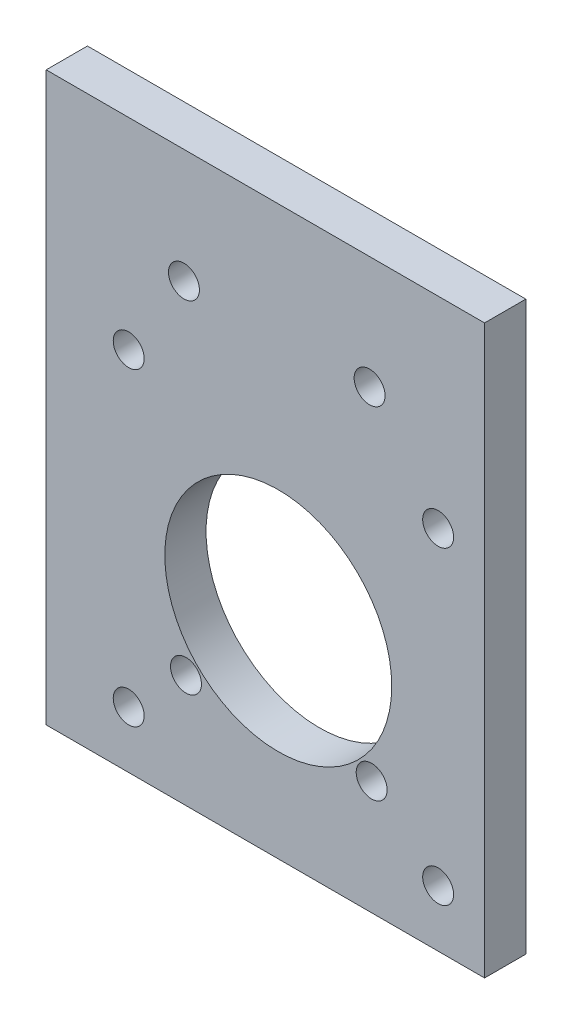
SolidWorks part; units mm, degrees
ref_plane "Front Plane" through (0, 0, 0) normal (0, 0, 1) x (1, 0, 0)
ref_plane "Top Plane" through (0, 0, 0) normal (0, 1, 0) x (1, 0, 0)
ref_plane "Right Plane" through (0, 0, 0) normal (1, 0, 0) x (0, 0, -1)
sketch "Sketch1" plane through (0, 0, 0) normal (0, 0, 1) x (1, 0, 0)
  line L1 (-21.25, 20) -> (21.25, 20)
  line L2 (-21.25, 20) -> (-21.25, -20)
  line L3 (-21.25, -20) -> (21.25, -20)
  line L4 (21.25, 20) -> (21.25, -20)
  line L5 (-21.25, 20) -> (21.25, -20) construction
  line L6 (-21.25, -20) -> (21.25, 20) construction
  point P0 (0, 0)
  dimension "D1" = 42.5
  dimension "D2" = 40
extrude "Boss-Extrude1" add sketch "Sketch1" along normal mid plane 4
sketch "Sketch2" plane through (0, 0, -2) normal (0, 0, -1) x (-1, 0, 0)
  circle A0 centre (-16.75, 15.5) radius 1.5
  circle A1 centre (13.25, 15.5) radius 1.5
  circle A2 centre (13.25, -14.5) radius 1.5
  circle A3 centre (-16.75, -14.5) radius 1.5
  circle A4 centre (-16.75, 15.5) radius 1.5 construction
  dimension "D1" = 0
extrude "Cut-Extrude1" cut sketch "Sketch2" against normal blind 4
sketch "Sketch3" plane through (0, 0, 2) normal (0, 0, 1) x (1, 0, 0)
  circle A7 centre (1.25, 0) radius 11
  circle A8 centre (1.25, 0) radius 11 construction
  dimension "D2" = 0
  dimension "D1" = 0
extrude "Cut-Extrude2" cut sketch "Sketch3" against normal blind 4
sketch "Sketch4" plane through (0, 20, 0) normal (0, 1, 0) x (1, 0, 0)
  line L1 (-21.25, 2) -> (21.25, 2)
  line L2 (-21.25, 2) -> (-21.25, -2)
  line L3 (-21.25, -2) -> (21.25, -2)
  line L4 (21.25, 2) -> (21.25, -2)
extrude "Boss-Extrude2" add sketch "Sketch4" along normal blind 15
sketch "Sketch7" plane through (0, 0, 2) normal (0, 0, 1) x (1, 0, 0)
  circle A0 centre (-7.894, 23.9455) radius 1.5
  circle A1 centre (10.1057, 24.0536) radius 1.5
  circle A2 centre (10.3039, -8.9458) radius 1.5
  circle A3 centre (-7.6958, -9.0539) radius 1.5
  dimension "D1" = 3
extrude "Cut-Extrude3" cut sketch "Sketch7" against normal blind 10
